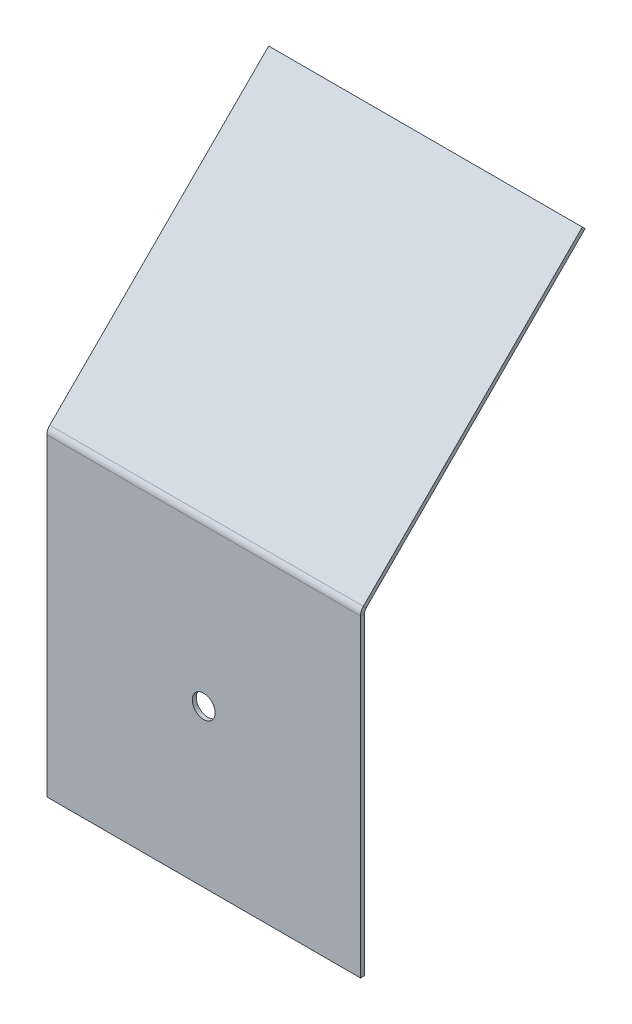
SolidWorks part; units mm, degrees
note: The reader was unsure of these and kept them because the rebuilt part matched: flange length of "Edge-Flange1".
ref_plane "Front Plane" through (0, 0, 0) normal (0, 0, 1) x (1, 0, 0)
ref_plane "Top Plane" through (0, 0, 0) normal (0, 1, 0) x (1, 0, 0)
ref_plane "Right Plane" through (0, 0, 0) normal (1, 0, 0) x (0, 0, -1)
sketch "Sketch1" plane through (0, 0, 0) normal (0, 0, 1) x (1, 0, 0)
  line L1 (-27.5, -27.5) -> (27.5, -27.5)
  line L2 (-27.5, -27.5) -> (-27.5, 27.5)
  line L3 (-27.5, 27.5) -> (27.5, 27.5)
  line L4 (27.5, -27.5) -> (27.5, 27.5)
  line L5 (-27.5, -27.5) -> (27.5, 27.5) construction
  line L6 (-27.5, 27.5) -> (27.5, -27.5) construction
  point P0 (0, 0)
  dimension "D1" = 55
  dimension "D2" = 55
base flange "Base-Flange1" sketch "Sketch1" thickness 0.7 reverse thickness direction no parameters "D1"=1
edge flange "Edge-Flange1" sketch "Sketch8" flange angle 135 flange length 55 flange position bend outside bend radius 1 thickness 0.7 parameters "D6"=0
sketch "Sketch8" plane through (0, 27.5, -0.7) normal (0, -0.7071, -0.7071) x (-1, 0, 0)
  line L1 (27.5, 0) -> (-27.5, 0) construction
  line L2 (-27.5, 0) -> (-27.5, 54.7101)
  line L3 (-27.5, 54.7101) -> (27.5, 54.7101)
  line L4 (27.5, 54.7101) -> (27.5, 0)
  line L5 (27.5, 0) -> (-27.5, 0)
bend "EdgeBend1" bend radius 1 bend angle 45 parameters "D5"=1
sketch "Sketch10" plane through (0, 0, 0) normal (0, 0, 1) x (1, 0, 0)
  circle A0 centre (0, 0) radius 2
extrude "Cut-Extrude1" cut sketch "Sketch10" against normal blind 10
sketch "Bend-Lines1" plane through (0, 0, 0) normal (0, 1, 0) x (1, 0, 0)
sketch "Bounding-Box1" plane through (0, 0, 0) normal (0, 1, 0) x (1, 0, 0)
sheet metal parameters "Sheet-Metal1" thickness 0.7 parameters "D1"=1
flat pattern "Flat-Pattern1" [suppressed]
sketch "Bend-Lines2" plane through (0, 0, 0) normal (0, 1, 0) x (1, 0, 0)
sketch "Bounding-Box2" [suppressed] plane through (0, 0, 0) normal (0, 1, 0) x (1, 0, 0)
sheet metal parameters "Sheet-Metal2" thickness 0.7 parameters "D1"=1
flat pattern "Flat-Pattern1" [suppressed]
sketch "Bend-Lines2" plane through (0, 0, 0) normal (0, 1, 0) x (1, 0, 0)
sketch "Bounding-Box2" [suppressed] plane through (0, 0, 0) normal (0, 1, 0) x (1, 0, 0)
bend of the flat pattern "Flatten-<EdgeBend1>1"
sheet metal parameters "Sheet-Metal3" thickness 0.7 parameters "D1"=1
flat pattern "Flat-Pattern1" [suppressed]
sketch "Bend-Lines2" plane through (0, 0, 0) normal (0, 1, 0) x (1, 0, 0)
sketch "Bounding-Box2" [suppressed] plane through (0, 0, 0) normal (0, 1, 0) x (1, 0, 0)
bend of the flat pattern "Flatten-<EdgeBend1>1"
